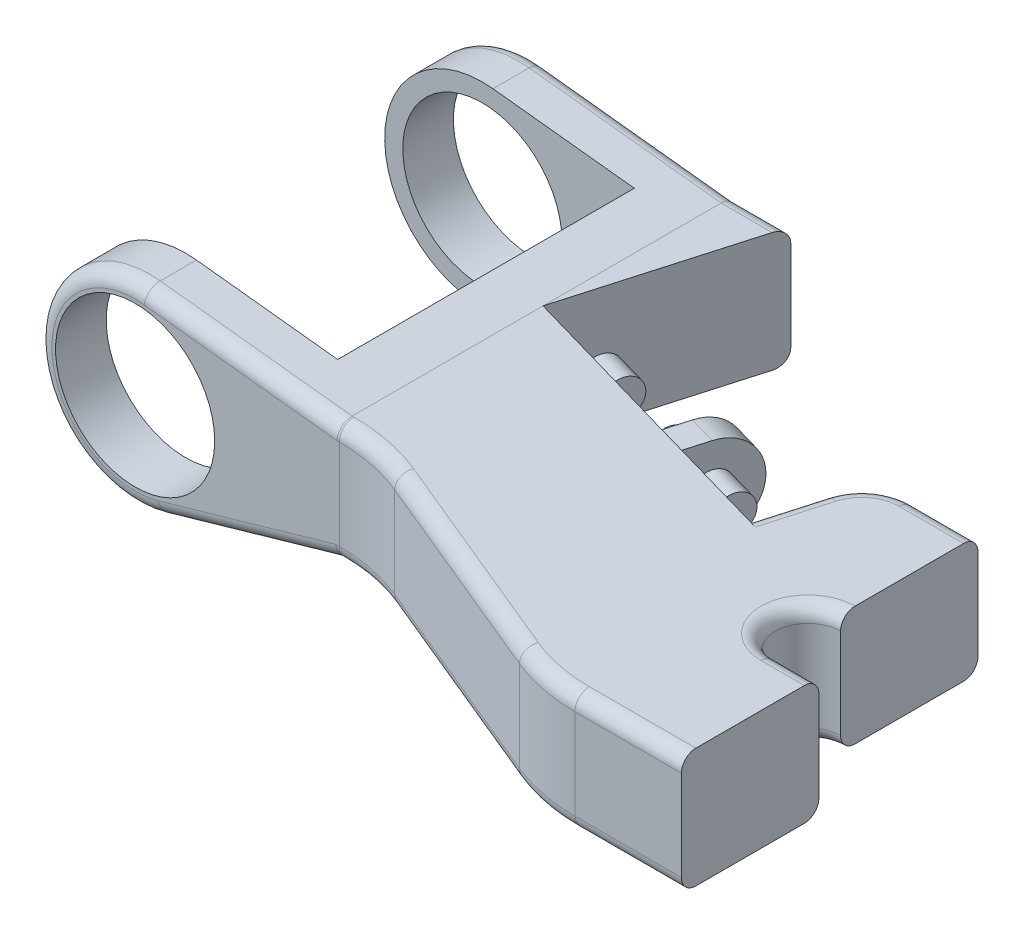
SolidWorks part; units mm, degrees
ref_plane "Спереди" through (0, 0, 0) normal (0, 0, 1) x (1, 0, 0)
ref_plane "Сверху" through (0, 0, 0) normal (0, 1, 0) x (1, 0, 0)
ref_plane "Справа" through (0, 0, 0) normal (1, 0, 0) x (0, 0, -1)
sketch "Эскиз8" plane through (0, 0, 0) normal (0, 1, 0) x (1, 0, 0)
  line L0 (-31.6673, 77.5) -> (-62.0836, 77.5) construction
  line L1 (-85, 43.6529) -> (-6, 21) construction
  line L2 (-106, 13.5) -> (-92.5, 13.5)
  line L3 (-92.5, 13.5) -> (-92.5, 6.5)
  line L4 (-92.5, 6.5) -> (-119.5, 6.5)
  line L6 (-119.5, 6.5) -> (-119.5, 13.5)
  line L7 (-119.5, 13.5) -> (-106, 13.5)
  line L8 (-117, 28.0456) -> (-95, 28.0456) construction
  line L31 (-92.5, 61.5) -> (-119.5, 61.5)
  line L32 (-119.5, 61.5) -> (-119.5, 54.5)
  line L33 (-119.5, 54.5) -> (-92.5, 54.5)
  line L34 (-92.5, 54.5) -> (-92.5, 61.5)
  line L37 (-62.0836, 77.5) -> (-62.0836, 61.5) construction
  line L38 (-62.0836, 61.5) -> (-92.5, 61.5) construction
  line L39 (-11.6673, -9.5) -> (-52.0836, -9.5) construction
  line L44 (-52.0836, -9.5) -> (-52.0836, 6.5) construction
  line L45 (-42.6378, 23.1833) -> (-38.3121, 21.943)
  line L46 (-17.6673, 16.0231) -> (-17.6673, 18.5) construction
  line L47 (-52.0836, 6.5) -> (-92.5, 6.5) construction
  line L48 (-106, 28.0456) -> (-85, 28.0456) construction
  line L52 (-92.5, 54.5) -> (-85, 54.5)
  line L53 (-85, 54.5) -> (-85, 13.5)
  line L54 (-85, 13.5) -> (-92.5, 13.5)
  line L56 (-6, 21) -> (-6, 28) construction
  line L59 (-78, 61.5) -> (-78, 63.0226)
  line L60 (-35.418, 32.0362) -> (-39.7436, 33.2766)
  line L61 (-78, 61.5) -> (-78, 33.3233)
  line L64 (-11.6673, 9.5) -> (-17.6673, 9.5)
  line L65 (-17.6673, 37.5) -> (-17.6673, 18.5) construction
  line L67 (-38.3121, 21.943) -> (-35.418, 32.0362)
  line L68 (-41.1218, 28.4703) -> (-42.6378, 23.1833) construction
  line L69 (-60.3189, 28.2533) -> (-57.4247, 38.3465) construction
  line L70 (-39.7436, 33.2766) -> (-41.1218, 28.4703)
  line L71 (-41.1218, 28.4703) -> (-36.7961, 27.2299)
  line L72 (-42.6378, 23.1833) -> (-78, 33.3233)
  line L79 (-38.3121, 21.943) -> (-17.6673, 16.0231) construction
  line L82 (-35.418, 32.0362) -> (-33.8512, 37.5) construction
  line L83 (-57.665, 38.4155) -> (-61.5101, 39.518)
  line L84 (-57.4247, 38.3465) -> (-57.665, 38.4155)
  line L85 (-57.4247, 38.3465) -> (-57.1844, 38.2776)
  line L86 (-57.1844, 38.2776) -> (-60.0786, 28.1844)
  line L87 (-61.5101, 39.518) -> (-62.8883, 34.7117)
  line L88 (-62.8883, 34.7117) -> (-58.5626, 33.4713)
  line L89 (-57.1844, 38.2776) -> (-53.3394, 37.1751)
  line L90 (-53.3394, 37.1751) -> (-56.2335, 27.0818)
  line L91 (-62.8883, 34.7117) -> (-64.4043, 29.4248) construction
  line L92 (-33.8512, 37.5) -> (-17.6673, 37.5) construction
  circle A1 centre (-106, 28.0456) radius 11
  circle A6 centre (-106, 28.0456) radius 13.5
  arc A8 (-17.6673, 18.5) -> (-17.6673, 9.5) centre (-17.6673, 14) ccw
  spline S0 degree 3 poles (-31.6673, 77.5) (-62.0836, 77.5) (-62.0836, 61.5) (-92.5, 61.5) knots 0 0 0 0 1 1 1 1
  spline S1 degree 3 poles (-11.6673, -9.5) (-52.0836, -9.5) (-52.0836, 6.5) (-92.5, 6.5) knots 0 0 0 0 1 1 1 1
  spline S3 degree 2 poles (-35.418, 32.0362) (-33.8512, 37.5) (-17.6673, 37.5) knots 0 0 0 1 1 1
  point P48 (-60.3189, 28.2533)
sketch "Эскиз10" plane through (0, 0, 0) normal (0, 1, 0) x (1, 0, 0)
  line L0 (-34.4146, 72.312) -> (-60.5171, 61.5) construction
  line L2 (-92.5, 61.5) -> (-78, 61.5)
  line L5 (-20.4853, 37.5) -> (-20.4853, 18.5)
  line L9 (-14.4853, 9.5) -> (-14.4853, -9.5)
  line L11 (-34.1789, -9.5) -> (-14.4853, -9.5)
  line L13 (-92.5, 54.5) -> (-85, 54.5)
  line L14 (-85, 54.5) -> (-85, 13.5)
  line L15 (-85, 13.5) -> (-92.5, 13.5)
  line L21 (-92.5, 6.5) -> (-72.8063, 6.5)
  line L22 (-14.4853, 9.5) -> (-20.4853, 9.5)
  line L23 (-20.4853, 9.5) -> (-20.4853, 18.5) construction
  line L31 (-53.4926, -9.5) -> (-53.4926, 6.5) construction
  line L32 (-92.5, 61.5) -> (-119.5, 61.5)
  line L34 (-92.5, 54.5) -> (-119.5, 54.5)
  line L35 (-119.5, 61.5) -> (-119.5, 54.5)
  line L36 (-92.5, 13.5) -> (-119.5, 13.5)
  line L38 (-92.5, 6.5) -> (-119.5, 6.5)
  line L39 (-119.5, 13.5) -> (-119.5, 6.5)
  line L41 (-53.4926, -1.5) -> (-72.8063, 6.5)
  line L42 (-53.4926, -1.5) -> (-34.1789, -9.5)
  line L46 (-29.3807, 37.5) -> (-20.4853, 37.5)
  line L47 (-15.6546, 17.0065) -> (-85, 36.8909) construction
  line L52 (-38.7777, 23.6369) -> (-36.297, 32.2883)
  line L60 (-78, 34.8837) -> (-60.3114, 29.8116)
  line L61 (-56.4663, 28.709) -> (-38.7777, 23.6369)
  line L62 (-75.5193, 43.5351) -> (-78, 34.8837)
  line L63 (-78, 61.5) -> (-70.3679, 61.5)
  line L64 (-70.3679, 61.5) -> (-75.5193, 43.5351)
  line L65 (-56.4663, 28.709) -> (-53.0209, 40.7248)
  line L66 (-53.0209, 40.7248) -> (-56.8659, 41.8274)
  line L67 (-56.8659, 41.8274) -> (-60.3114, 29.8116)
  arc A0 (-20.4853, 18.5) -> (-20.4853, 9.5) centre (-20.4853, 14) ccw
  arc A8 (-36.297, 32.2883) -> (-29.3807, 37.5) centre (-29.3807, 30.3051) cw
  arc A9 (-20.4853, 37.5) -> (-38.7777, 23.6369) centre (-20.4853, 18.5) ccw construction
  point P33 (0, 0)
  point P34 (0, 0)
  point P36 (0, 0)
extrude "Бобышка-Вытянуть1" add sketch "Эскиз10" along normal mid plane 27 separate body contours L32 L35 L34 L13 L14 L15 L36 L39 L38 region at (-59.6166, 0, -20.8546)
sketch "Эскиз11" plane through (0, 0, 0) normal (0, 0, 1) x (1, 0, 0)
  line L10 (-11.6673, -6) -> (-11.6673, 10.5)
  line L16 (-106, 0) -> (-11.6673, 0) construction
  line L31 (-11.6673, 10.5) -> (-78, 10.5)
  line L50 (-119.5, 13.5) -> (-11.6673, 13.5)
  line L51 (-119.5, 13.5) -> (-119.5, -13.5)
  line L52 (-119.5, -13.5) -> (-11.6673, -13.5)
  line L53 (-11.6673, 13.5) -> (-11.6673, -13.5)
  line L55 (-78, 10.5) -> (-78, -6)
  line L56 (-78, -6) -> (-11.6673, -6)
  line L57 (-78, -6) -> (-102.2714, -12.9749)
  line L58 (-78, 10.5) -> (-104.5232, 13.419)
  circle A2 centre (-106, 0) radius 11
  circle A5 centre (-106, 0) radius 13.5
extrude "Вырез-Вытянуть1" cut sketch "Эскиз11" against normal through all both and the other way through all contours A2 | A5 L51 L52 | A5 L50 L51 | L52 L53 | L50 L53 region at (-51.7306, -9.9565, 0) region at (-52.0379, 12.0853, 0) region at (-116.4845, -10.4845, 0) region at (-116.4845, 10.4845, 0) region at (-106, 0, 0)
sketch "Эскиз12" plane through (-63.628, 0, -18.245) normal (-0.9613, 0, -0.2756) x (-0.2756, 0, 0.9613)
  line L0 (-18.5327, 0) -> (-18.5327, -6) construction
  line L1 (-21.0327, 0) -> (-18.5327, 0) construction
  circle A0 centre (-18.5327, 0) radius 2.5
extrude "Бобышка-Вытянуть2" add sketch "Эскиз12" along normal blind 4.5
sketch "Эскиз13" plane through (-42.0943, 0, -12.0704) normal (-0.9613, 0, -0.2756) x (-0.2756, 0, 0.9613)
  line L0 (-21.0327, 0) -> (-18.5327, 0) construction
  line L2 (-18.5327, 0) -> (-18.5327, -6) construction
  circle A0 centre (-18.5327, 0) radius 2.5
extrude "Бобышка-Вытянуть3" add sketch "Эскиз13" along normal blind 4.5
fillet "Скругление1" radius 25 2 edges at (-34.1789, 2.25, 9.5) (-72.8063, 2.25, -6.5)
sketch "Эскиз21" plane through (-81.3167, 0, -23.3172) normal (0.9613, 0, 0.2756) x (0.2756, 0, -0.9613)
  line L0 (12.0327, -6) -> (18.5327, -6)
  line L1 (12.0327, -6) -> (39.7216, -6) construction
  line L2 (18.5327, -6) -> (18.5327, 0)
  circle A0 centre (18.5327, 0) radius 2.5
extrude "Бобышка-Вытянуть5" add sketch "Эскиз21" along normal blind 4.5 contours A0 region at (-75.7349, -1.7178, -42.7831)
sketch "Эскиз22" plane through (-59.783, 0, -17.1425) normal (0.9613, 0, 0.2756) x (0.2756, 0, -0.9613)
  line L0 (12.0327, -6) -> (18.5327, -6)
  line L2 (18.5327, -6) -> (18.5327, 0)
  circle A0 centre (18.5327, 0) radius 2.5
extrude "Бобышка-Вытянуть6" add sketch "Эскиз22" along normal blind 4.5 contours A0 region at (-54.2012, -1.7178, -36.6085)
sketch "Эскиз24" plane through (-59.783, 0, -17.1425) normal (0.9613, 0, 0.2756) x (0.2756, 0, -0.9613)
  line L0 (18.5327, -6) -> (24.5327, -6)
  line L1 (24.5327, -6) -> (24.5327, 0)
  line L2 (24.5327, 0) -> (24.5327, 10.5)
  line L3 (24.5327, 10.5) -> (12.0327, 10.5)
  line L5 (18.5327, 6) -> (12.0327, 6)
  line L6 (12.0327, 10.5) -> (12.0327, 6)
  circle A0 centre (18.5327, 0) radius 6
  line M2 (12.0327, -6) -> (24.5327, -6)
  line M3 (24.5327, -6) -> (24.5327, 10.5)
  line M4 (24.5327, 10.5) -> (12.0327, 10.5)
  line M5 (12.0327, 10.5) -> (12.0327, -6)
extrude "Вырез-Вытянуть5" cut sketch "Эскиз24" against normal blind 4 contours A0 L5 M3 M4 M5 | A0 M2 M3 region at (-53.3903, -4.6598, -39.4365) region at (-54.5802, 7.8164, -35.2869)
fillet "Скругление6" radius 2 28 edges at (-37.5373, -6, -27.9626) (-33.7108, -6, -36.0512) (-37.5373, 10.5, -27.9626) (-33.7108, 10.5, -36.0512) (-53.4926, -6, 1.5) (-34.0834, -6, 9.0196) (-72.9019, 10.5, -6.0196) (-53.4926, 10.5, 1.5) (-34.0834, 10.5, 9.0196) (-17.4853, -6, -9.5) (-17.4853, 10.5, -9.5) (-24.933, -6, -37.5) (-24.933, 10.5, -37.5) (-21.8457, -6, 9.5) (-21.8457, 10.5, 9.5) (-24.9853, -6, -14) (-24.9853, 10.5, -14) (-72.9019, -6, -6.0196) (-91.2616, 11.9595, -61.5) (-90.1357, -9.4874, -61.5) (-90.1357, -9.4874, -6.5) (-119.4511, -1.1476, -6.5) (-77.8896, -6, -6.5) (-77.8896, 10.5, -6.5) (-74.184, -6, -61.5) (-74.184, 10.5, -61.5) (-119.4511, -1.1476, -61.5) (-91.2616, 11.9595, -6.5)
